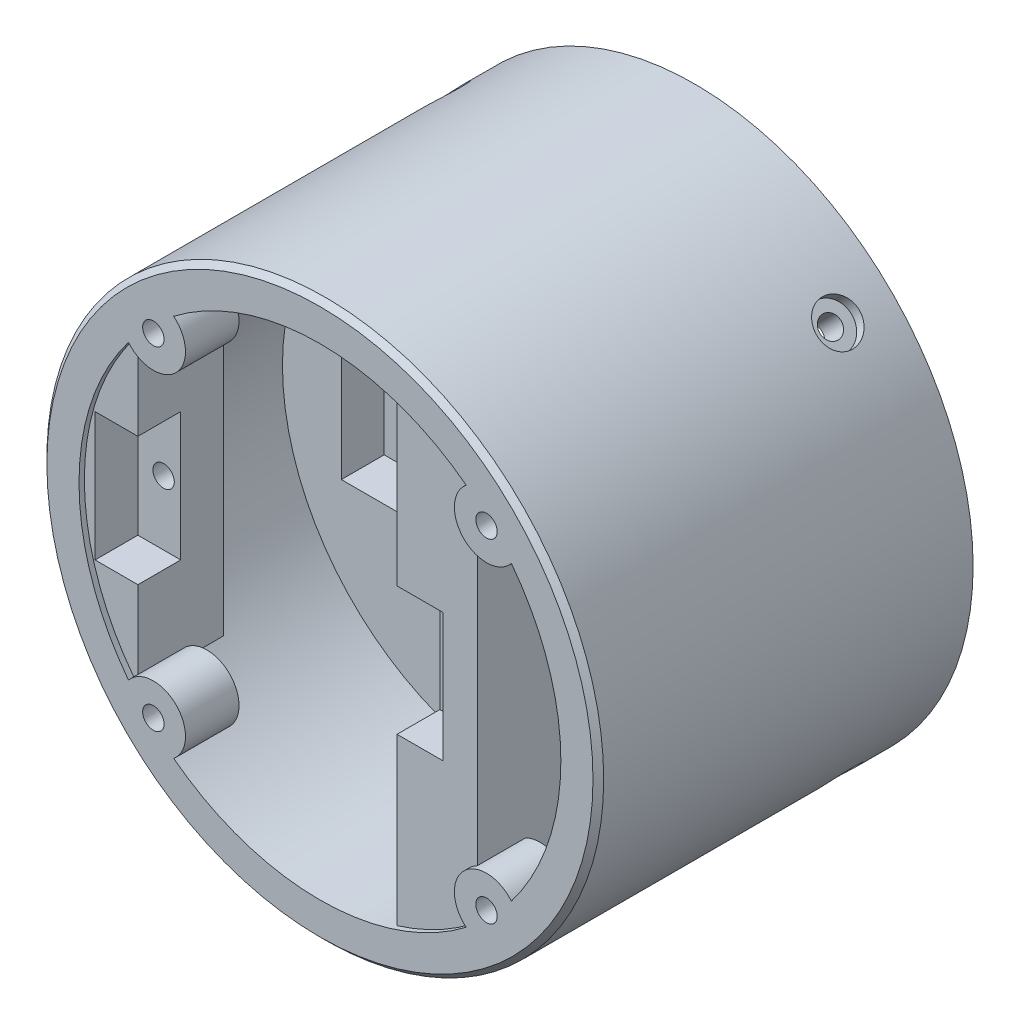
SolidWorks part; units mm, degrees
material "ABS"
ref_plane "Спереди" through (0, 0, 0) normal (0, 0, 1) x (1, 0, 0)
ref_plane "Сверху" through (0, 0, 0) normal (0, 1, 0) x (1, 0, 0)
ref_plane "Справа" through (0, 0, 0) normal (1, 0, 0) x (0, 0, -1)
sketch "Эскиз1" plane through (0, 0, 0) normal (0, 0, 1) x (1, 0, 0)
  circle A1 centre (0, 0) radius 26
  dimension "D1" = 52
extrude "Бобышка-Вытянуть1" add sketch "Эскиз1" along normal blind 35
sketch "Эскиз3" plane through (0, 0, 0) normal (0, 0, -1) x (-1, 0, 0)
  circle A0 centre (0, 0) radius 22.5
  dimension "D1" = 45
extrude "Вырез-Вытянуть1" cut sketch "Эскиз3" against normal blind 11 contours A0
sketch "Эскиз10" plane through (0, 0, 11) normal (0, 0, -1) x (-1, 0, 0)
  circle A0 centre (0, 0) radius 15
  dimension "D1" = 30
sketch "Эскиз4" plane through (0, 0, 35) normal (0, 0, 1) x (1, 0, 0)
  circle A0 centre (0, 0) radius 22.5
  dimension "D1" = 45
extrude "Вырез-Вытянуть2" cut sketch "Эскиз4" against normal offset from surface (19 mm away) 5 up to face at (-22.5, 0, 11)
sketch "Эскиз13" plane through (0, 0, 16) normal (0, 0, 1) x (1, 0, 0)
  line L0 (0, 26) -> (0, -26) construction
  line L1 (-26, 0) -> (26, 0) construction
  line L3 (-17, 6.5) -> (7, 6.5)
  line L4 (-17, 6.5) -> (-17, -6.5)
  line L5 (-17, -6.5) -> (7, -6.5)
  line L6 (7, 6.5) -> (7, -6.5)
  circle A0 centre (0, 0) radius 26 construction
  point P11 (-17, 0)
  point P13 (-5, 6.5)
  dimension "D1" = 13
  dimension "D2" = 24
  dimension "D3" = 5
extrude "Вырез-Вытянуть3" cut sketch "Эскиз13" against normal blind 4
sketch "Эскиз12" plane through (0, 0, 35) normal (0, 0, 1) x (1, 0, 0)
  line L0 (0, 26) -> (0, -26) construction
  line L1 (0, 0) -> (28.1458, 16.25) construction
  line L2 (-26, 0) -> (32.5, 0) construction
  line L5 (19.4856, 11.25) -> (22.5167, 13)
  line L6 (19.4856, -11.25) -> (22.5167, -13)
  circle A0 centre (0, 0) radius 26 construction
  arc A4 (19.4856, -11.25) -> (19.4856, 11.25) centre (0, 0) ccw
  arc A6 (22.5167, -13) -> (22.5167, 13) centre (0, 0) ccw
  dimension "D1" = 30
ref_plane "Плоскость2" through (0, 0, 26.5) normal (0, 0, 1) x (1, 0, 0)
sketch "Эскиз14" plane through (0, 0, 26.5) normal (0, 0, 1) x (1, 0, 0)
  line L1 (7, 0) -> (-46.5151, 0) construction
  line L2 (7, -6.5) -> (7, 6.5) construction
  line L3 (-17.5, -28.5313) -> (-17.5, 17.8536) construction
  line L6 (7, 0) -> (57.6607, 0) construction
  line L8 (14.2, -44.5711) -> (14.2, 20) construction
  line L10 (14.2, -20.5757) -> (14.2, 20.5757)
  line L13 (-17.5, -17.8536) -> (-17.5, 17.8536)
  line L15 (6.7, -24.0855) -> (6.7, 24.0855)
  line L16 (0, -28.5313) -> (0, 28.5313) construction
  arc A4 (-17.5, 17.8536) -> (-17.5, -17.8536) centre (0, 0) ccw
  arc A5 (14.2, 20.5757) -> (6.7, 24.0855) centre (0, 0) ccw
  arc A6 (6.7, -24.0855) -> (14.2, -20.5757) centre (0, 0) ccw
  point P11 (-17.5, 0)
  point P18 (7, 0)
  point P22 (14.2, 0)
  point P27 (14.2, 0)
  point P29 (-17.5, 0)
  point P33 (7.5, 0)
  point P34 (6.7, 0)
  point P35 (0, 0)
  dimension "D1" = 17.5
  dimension "D4" = 6.7
extrude "Бобышка-Вытянуть2" add sketch "Эскиз14" along normal blind 8
sketch "Эскиз15" plane through (0, 0, 34.5) normal (0, 0, 1) x (1, 0, 0)
  line L0 (43.3889, 0) -> (-43.3889, 0) construction
  line L1 (0, 36.1435) -> (0, -36.1435) construction
  line L2 (-21.5, 29.8665) -> (-21.5, -29.8665) construction
  line L3 (11, 32.0712) -> (11, -32.0712) construction
  line L4 (-17.5, 23.7559) -> (-17.5, -23.2484) construction
  line L5 (-21.5, -6) -> (-21.5, 6)
  line L6 (-21.5, 6) -> (-17.5, 6)
  line L7 (6.7, 41.39) -> (6.7, -19.4927) construction
  line L8 (6.7, 21.4793) -> (6.7, -21.4793) construction
  line L9 (11, -6) -> (11, 6)
  line L10 (11, 6) -> (6.7, 6)
  line L11 (-17.5, 6) -> (-17.5, -6)
  line L12 (6.7, 6) -> (6.7, -6)
  line L13 (11, -6) -> (6.7, -6)
  line L14 (-21.5, -6) -> (-17.5, -6)
  point P4 (0, 0)
  point P8 (0, 0)
  point P11 (-21.5, 0)
  point P14 (11, 0)
  point P19 (-17.5, 0.2537)
  point P24 (6.7, 10.9487)
  point P30 (6.7, 0)
  point P31 (11, 0)
  point P32 (-17.5, 0)
  point P33 (-21.5, 0)
  dimension "D1" = 21.5
  dimension "D2" = 11
  dimension "D3" = 6
  dimension "D4" = 6
extrude "Вырез-Вытянуть5" cut sketch "Эскиз15" along direction (0, 0, 1) on the side against the normal offset from surface (4 mm away) 18.5 up to face at (-5, 0, 12)
sketch "Эскиз17" plane through (0, 0, 30.5) normal (0, 0, 1) x (1, 0, 0)
  circle A1 centre (-19.1, 0) radius 1
  circle A2 centre (8.6, 0) radius 1
extrude "Вырез-Вытянуть6" cut sketch "Эскиз17" along direction (0, 0, 1) on the side against the normal up to surface (4 mm away) up to face at (10.5461, 0, 26.5)
sketch "Эскиз20" plane through (0, 0, 35) normal (0, 0, 1) x (1, 0, 0)
  line L0 (-57.2124, 0) -> (57.2124, 0) construction
  line L1 (0, 34.3681) -> (0, -34.3681) construction
  line L2 (0, 0) -> (-44.2288, 44.2288) construction
  circle A0 centre (0, 0) radius 22 construction
  circle A2 centre (0, 0) radius 26 construction
  circle A3 centre (-15.5563, 15.5563) radius 3
  circle A4 centre (15.5563, 15.5563) radius 3
  circle A5 centre (15.5563, -15.5563) radius 3
  circle A6 centre (-15.5563, -15.5563) radius 3
  point P3 (-15.5563, 15.5563)
  point P8 (0, 0)
  point P12 (0, 0)
  point P23 (0, 0)
  point P27 (0, 0)
  dimension "D2" = 52
  dimension "D3" = 22
  dimension "D1" = 6
  dimension "D4" = 4
extrude "Бобышка-Вытянуть3" add sketch "Эскиз20" against normal blind 5
sketch "Эскиз21" plane through (0, 0, 35) normal (0, 0, 1) x (1, 0, 0)
  circle A4 centre (-15.5563, 15.5563) radius 1
  circle A11 centre (15.5563, 15.5563) radius 1
  circle A12 centre (15.5563, -15.5563) radius 1
  circle A13 centre (-15.5563, -15.5563) radius 1
  point P11 (-0.7071, 0)
  point P12 (0, 0)
  point P14 (0.7071, 0)
  point P15 (0, 0)
  dimension "D1" = 2
  dimension "D2" = 4
extrude "Вырез-Вытянуть9" cut sketch "Эскиз21" against normal blind 5
sketch "Эскиз24" plane through (0, 0, 16) normal (0, 0, 1) x (1, 0, 0)
  line L0 (7, -6.5) -> (7, 6.5) construction
  line L1 (11, 4) -> (13.5, 4)
  line L2 (11, 4) -> (11, -4)
  line L3 (11, -4) -> (13.5, -4)
  line L4 (13.5, 4) -> (13.5, -4)
  point P7 (11, 0)
  point P10 (7, 0)
  dimension "D1" = 2.5
  dimension "D2" = 8
  dimension "D4" = 4
extrude "Вырез-Вытянуть12" cut sketch "Эскиз24" against normal up to surface (5 mm away) up to face at (-22.5, 0, 11)
ref_plane "Плоскость3" through (-18.3848, -18.3848, 35) normal (-0.7071, -0.7071, 0) x (-0.7071, 0.7071, 0)
sketch "Эскиз25" plane through (-18.3848, -18.3848, 35) normal (-0.7071, -0.7071, 0) x (-0.7071, 0.7071, 0)
  line L0 (0, 0) -> (0, 35) construction
  circle A0 centre (0, 30) radius 2
  dimension "D1" = 4
  dimension "D2" = 5
extrude "Вырез-Вытянуть13" cut sketch "Эскиз25" against normal blind 1
sketch "Эскиз26" plane through (-17.6777, -17.6777, 0) normal (-0.7071, -0.7071, 0) x (0, 0, 1)
  circle A0 centre (5, 0) radius 1
  dimension "D1" = 2
extrude "Вырез-Вытянуть14" cut sketch "Эскиз26" against normal through all
pattern_circular "Круговой массив1" count 4 over 360 about axis through (0, 0, 35) along (0, 0, -1) of "Вырез-Вытянуть14", "Вырез-Вытянуть13"
chamfer "Фаска1" distance 0.5 angle 45 1 edges at (-22.5, 0, 0)
chamfer "Фаска2" distance 0.5 angle 45 1 edges at (26, 0, 35)
